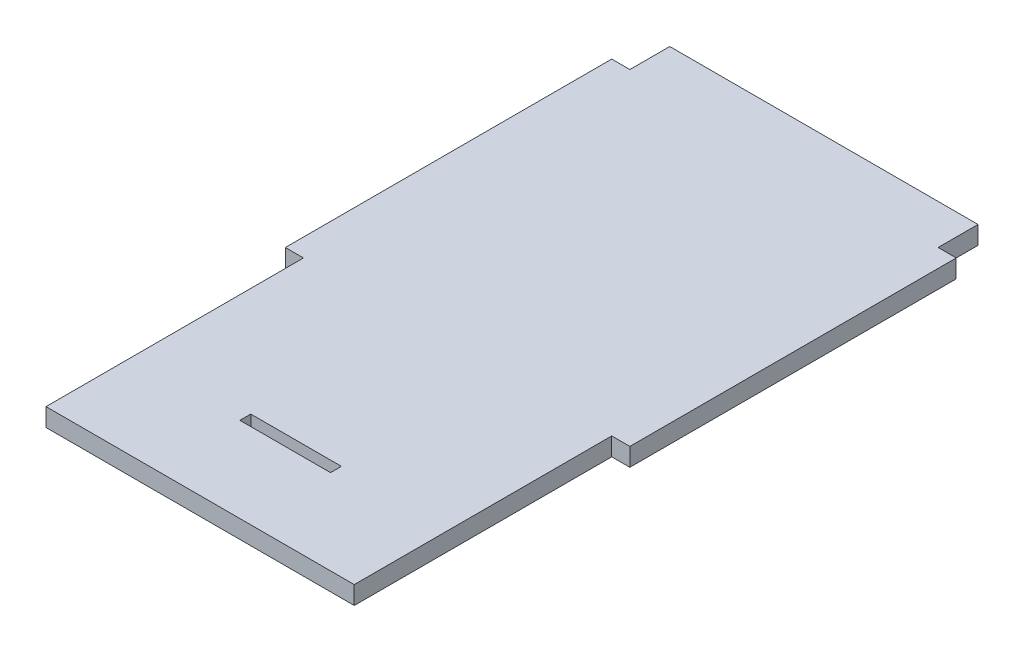
SolidWorks part; units mm, degrees
ref_plane "Alzado" through (0, 0, 0) normal (0, 0, 1) x (1, 0, 0)
ref_plane "Planta" through (0, 0, 0) normal (0, 1, 0) x (1, 0, 0)
ref_plane "Vista lateral" through (0, 0, 0) normal (1, 0, 0) x (0, 0, -1)
sketch "Croquis1" plane through (0, 0, 0) normal (0, 1, 0) x (1, 0, 0)
  line L0 (-42.5, -15) -> (42.5, -15) construction
  line L1 (-42.5, -86) -> (42.5, -86)
  line L2 (-42.5, -86) -> (-42.5, -15)
  line L3 (-42.5, 86) -> (42.5, 86)
  line L4 (42.5, -86) -> (42.5, -15)
  line L5 (-42.5, -86) -> (42.5, 86) construction
  line L6 (-42.5, 86) -> (42.5, -86) construction
  line L7 (-42.5, 75) -> (-42.5, 86)
  line L8 (-42.5, -15) -> (-47.5, -15)
  line L9 (42.5, 75) -> (42.5, 86)
  line L10 (-42.5, 75) -> (-47.5, 75)
  line L11 (-47.5, -15) -> (-47.5, 75)
  line L12 (42.5, 75) -> (47.5, 75)
  line L13 (0, 86) -> (0, -86) construction
  line L14 (42.5, -15) -> (47.5, -15)
  line L15 (47.5, 75) -> (47.5, -15)
  line L17 (-12.5, -62.5396) -> (12.5, -62.5396)
  line L18 (-12.5, -62.5396) -> (-12.5, -59.5396)
  line L19 (-12.5, -59.5396) -> (12.5, -59.5396)
  line L20 (12.5, -62.5396) -> (12.5, -59.5396)
  line L21 (-12.5, -62.5396) -> (12.5, -59.5396) construction
  line L22 (-12.5, -59.5396) -> (12.5, -62.5396) construction
  point P0 (0, 0)
  point P16 (0, -61.0396)
  dimension "D1" = 172
  dimension "D2" = 85
  dimension "D3" = 71
  dimension "D4" = 90
  dimension "D5" = 5
  dimension "D6" = 5
  dimension "D7" = 25
  dimension "D8" = 3
extrude "Saliente-Extruir1" add sketch "Croquis1" along normal blind 5
